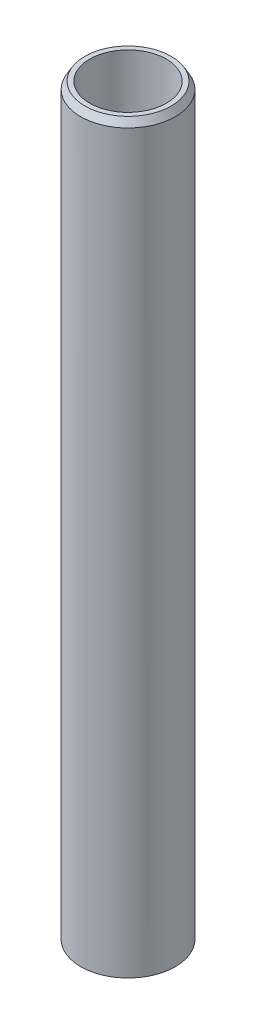
SolidWorks part; units mm, degrees
ref_plane "Front Plane" through (0, 0, 0) normal (0, 0, 1) x (1, 0, 0)
ref_plane "Top Plane" through (0, 0, 0) normal (0, 1, 0) x (1, 0, 0)
ref_plane "Right Plane" through (0, 0, 0) normal (1, 0, 0) x (0, 0, -1)
sketch "Sketch1" plane through (0, 0, 0) normal (0, 1, 0) x (1, 0, 0)
  circle A0 centre (0, 0) radius 25
  dimension "SHAFT_OD" = 50
extrude "Boss-Extrude1" add sketch "Sketch1" along normal blind 394.9062
sketch "Sketch2" plane through (0, 0, 0) normal (0, 1, 0) x (1, 0, 0)
  circle A0 centre (0, 0) radius 20.2399
  dimension "BORE_D" = 40.4798
extrude "Cut-Extrude1" cut sketch "Sketch2" along normal through all
chamfer "Chamfer1" distance 3.7721 angle 30.465 2 edges at (0, 394.9062, 25) (0, 0, 25) first distance on face at (0, 394.9062, 25) first distance on face at (0, 0, 20.2399)
